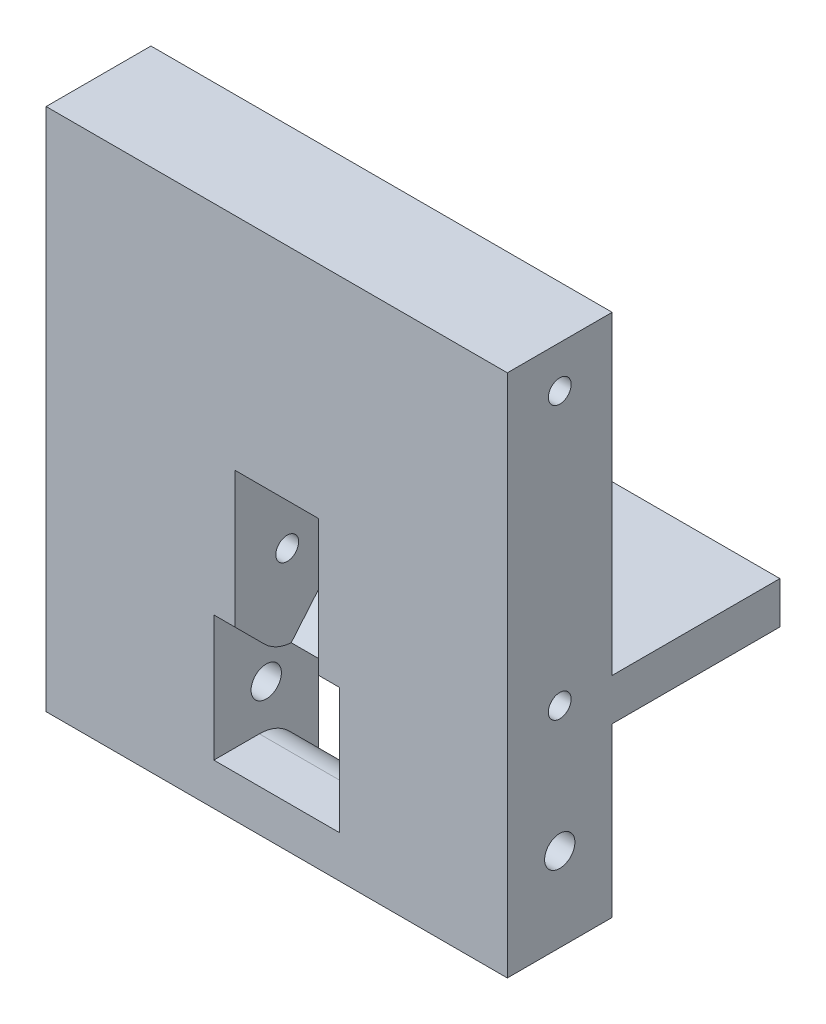
SolidWorks part; units mm, degrees
material "ABS"
ref_plane "Front Plane" through (0, 0, 0) normal (0, 0, 1) x (1, 0, 0)
ref_plane "Top Plane" through (0, 0, 0) normal (0, 1, 0) x (1, 0, 0)
ref_plane "Right Plane" through (0, 0, 0) normal (1, 0, 0) x (0, 0, -1)
sketch "Sketch2" plane through (-62.0532, 0, 0) normal (-1, 0, 0) x (0, 0, 1)
  line L1 (9.2122, 119.5977) -> (25.0872, 119.5977)
  line L2 (9.2122, 119.5977) -> (9.2122, 40.2227)
  line L3 (9.2122, 40.2227) -> (25.0872, 40.2227)
  line L4 (9.2122, 65.6227) -> (-92.3878, 65.6227)
  line L5 (-92.3878, 65.6227) -> (-92.3878, 59.2727)
  line L6 (-92.3878, 59.2727) -> (9.2122, 59.2727)
  line L7 (9.2122, 59.2727) -> (9.2122, 65.6227)
  line L8 (9.2122, 65.6227) -> (-92.3878, 65.6227)
  line L9 (-92.3878, 65.6227) -> (-92.3878, 59.2727)
  line L10 (-92.3878, 59.2727) -> (9.2122, 59.2727)
  line L11 (9.2122, 59.2727) -> (9.2122, 65.6227)
  line L12 (25.0872, 119.5977) -> (25.0872, 40.2227)
  line L13 (9.2122, 65.6227) -> (-16.1878, 65.6227)
  line L14 (9.2122, 65.6227) -> (9.2122, 71.9727)
  line L15 (9.2122, 71.9727) -> (-16.1878, 71.9727)
  line L16 (-16.1878, 65.6227) -> (-16.1878, 71.9727)
  line L17 (15.5622, 114.8352) -> (18.7372, 114.8352) construction
  line L18 (15.5622, 114.8352) -> (15.5622, 111.6602) construction
  line L19 (15.5622, 111.6602) -> (18.7372, 111.6602) construction
  line L20 (18.7372, 114.8352) -> (18.7372, 111.6602) construction
  line L21 (15.5622, 114.8352) -> (18.7372, 111.6602) construction
  line L22 (15.5622, 111.6602) -> (18.7372, 114.8352) construction
  line L23 (15.5622, 73.5602) -> (18.7372, 73.5602) construction
  line L24 (15.5622, 73.5602) -> (15.5622, 70.3852) construction
  line L25 (15.5622, 70.3852) -> (18.7372, 70.3852) construction
  line L26 (18.7372, 73.5602) -> (18.7372, 70.3852) construction
  line L27 (15.5622, 73.5602) -> (18.7372, 70.3852) construction
  line L28 (15.5622, 70.3852) -> (18.7372, 73.5602) construction
  circle A0 centre (17.1497, 71.9727) radius 2.3 construction
  circle A1 centre (17.1497, 113.2477) radius 1.7272
  circle A2 centre (17.1497, 71.9727) radius 1.7272
  line M10 (9.2122, 65.6227) -> (-92.3878, 65.6227)
  line M13 (9.2122, 59.2727) -> (9.2122, 65.6227)
  dimension "D5" = 4.6
  dimension "D8" = 3.4544
  dimension "D9" = 7.9375
  dimension "D10" = 3.175
  dimension "D7" = 6.35
  dimension "D15" = 3.4544
  dimension "D2" = 79.375
  dimension "D3" = 19.05
  dimension "D4" = 15.875
  dimension "D6" = 7.9375
  dimension "D11" = 25.4
  dimension "D12" = 6.35
  dimension "D13" = 3.175
  dimension "D14" = 41.275
  dimension "D1" = 0
extrude "Boss-Extrude1" add sketch "Sketch2" against normal blind 69.85 contours L16 L2 L15 M10 | L12 L1 L2 L3 A1 A0 M13 region at (-62.0532, 79.7185, 17.1497) region at (-62.0532, 68.7977, -3.4878)
sketch "Sketch3" plane through (0, 0, 9.2122) normal (0, 0, -1) x (-1, 0, 0)
  line L2 (17.6032, 46.5727) -> (36.6532, 46.5727)
  line L3 (17.6032, 46.5727) -> (17.6032, 59.2727)
  line L4 (62.0532, 40.2227) -> (62.0532, 65.6227)
  line L5 (62.0532, 65.6227) -> (-7.7968, 65.6227)
  line L6 (-7.7968, 65.6227) -> (-7.7968, 40.2227)
  line L7 (-7.7968, 40.2227) -> (62.0532, 40.2227)
  line L8 (62.0532, 40.2227) -> (62.0532, 65.6227)
  line L9 (62.0532, 65.6227) -> (-7.7968, 65.6227)
  line L10 (-7.7968, 65.6227) -> (-7.7968, 40.2227)
  line L11 (-7.7968, 40.2227) -> (62.0532, 40.2227)
  line L12 (17.6032, 59.2727) -> (36.6532, 59.2727)
  line L13 (36.6532, 46.5727) -> (36.6532, 59.2727)
  line L14 (17.6032, 46.5727) -> (36.6532, 59.2727) construction
  line L15 (17.6032, 59.2727) -> (36.6532, 46.5727) construction
  point P6 (27.1282, 40.2227)
  point P7 (27.1282, 52.9227)
  dimension "D2" = 19.05
  dimension "D3" = 12.7
  dimension "D4" = 12.7
  dimension "D1" = 0
extrude "Cut-Extrude1" cut sketch "Sketch3" against normal blind 127 contours L2 L13 L12 L3
sketch "Sketch4" plane through (7.7968, 0, 0) normal (1, 0, 0) x (0, 0, -1)
  line L0 (-9.2122, 40.2227) -> (-25.0872, 40.2227) construction
  line L1 (-25.0872, 52.9227) -> (-17.1497, 52.9227) construction
  line L2 (-25.0872, 52.9227) -> (-25.0872, 59.2727) construction
  line L3 (-25.0872, 59.2727) -> (-17.1497, 59.2727) construction
  line L4 (-17.1497, 52.9227) -> (-17.1497, 59.2727) construction
  line L5 (-25.0872, 46.5727) -> (-9.2122, 46.5727)
  line L7 (-9.2122, 46.5727) -> (-9.2122, 59.2727)
  line L8 (-9.2122, 59.2727) -> (-25.0872, 59.2727)
  line L9 (-25.0872, 59.2727) -> (-25.0872, 46.5727)
  line L10 (-25.0872, 46.5727) -> (-9.2122, 46.5727) construction
  line L12 (-9.2122, 46.5727) -> (-9.2122, 59.2727) construction
  line L13 (-9.2122, 59.2727) -> (-25.0872, 59.2727) construction
  line L14 (-25.0872, 59.2727) -> (-25.0872, 46.5727) construction
  circle A0 centre (-17.1497, 52.9227) radius 2.2951
  dimension "D2" = 4.5901
  dimension "D3" = 12.7
  dimension "D1" = 0
extrude "Cut-Extrude2" cut sketch "Sketch4" against normal blind 127 contours A0
chamfer "Chamfer1" distance 6.35 angle 45 2 edges at (-27.1282, 46.5727, 9.2122) (-27.1282, 59.2727, 25.0872)
fillet "Fillet2" radius 6.35 2 edges at (-27.1282, 46.5727, 15.5622) (-27.1282, 59.2727, 18.7372)
sketch "Sketch8" plane through (-27.1282, 59.2727, 33.483) normal (-1, 0, 0) x (0, 0, 1)
  line L0 (-24.2707, 12.7) -> (-49.6707, 12.7) construction
  line L1 (-24.2707, 12.7) -> (-49.6707, 12.7)
  line L2 (-2.8258, 22.4609) -> (-2.8258, 22.4965)
  line L3 (-15.9276, 35.8951) -> (9.2394, 5.9023)
  line L4 (9.2394, 5.9023) -> (-7.0779, -7.7896)
  line L5 (-7.0779, -7.7896) -> (-20.0855, 7.7123)
  line L6 (-20.0855, 7.7123) -> (-24.2707, 12.7)
  line L7 (-7.0779, -7.7896) -> (-24.2707, 12.7)
  line L8 (-7.0779, -7.7896) -> (-9.0237, -9.4222)
  line L9 (-24.2707, 12.7) -> (-26.2165, 11.0673)
  line L10 (-9.0237, -9.4222) -> (-26.2165, 11.0673)
  line L11 (-26.2165, 11.0673) -> (-27.5864, 12.7)
  circle A0 centre (-30.5207, 23.65) radius 2.4 construction
  circle A1 centre (-30.5207, 23.65) radius 2.4
  circle A2 centre (-30.5207, 23.65) radius 19.05
  dimension "D1" = 38.1
  dimension "D2" = 130
  dimension "D3" = 2.54
extrude "Cut-Extrude3" cut sketch "Sketch8" against normal blind 6.35 and the other way blind 6.35 contours A2 L10 L8 L5 | L10 A2 L6 L9 | L11 L9 L1 | A2 L5 L4 L3 | L6 A2 L1 A1 region at (-27.1282, 71.4285, 7.4584) region at (-27.1282, 72.49, 7.5544) region at (-27.1282, 68.752, 10.2779) region at (-27.1282, 68.3478, 27.4388) region at (-27.1282, 58.4952, 18.8569)
sketch "Sketch10" plane through (0, 0, 9.2122) normal (0, 0, -1) x (-1, 0, 0)
  line L0 (33.4782, 71.9727) -> (62.0532, 71.9727) construction
  line L1 (41.4998, 71.9727) -> (51.0248, 71.9727)
  line L2 (41.4998, 71.9727) -> (41.4998, 76.6717)
  line L3 (41.4998, 76.6717) -> (51.0248, 76.6717)
  line L4 (51.0248, 71.9727) -> (51.0248, 76.6717)
  line L5 (41.4998, 104.6609) -> (51.0248, 104.6609)
  line L6 (41.4998, 104.6609) -> (41.4998, 99.9619)
  line L7 (41.4998, 99.9619) -> (51.0248, 99.9619)
  line L8 (51.0248, 104.6609) -> (51.0248, 99.9619)
  line L9 (62.0532, 119.5977) -> (62.0532, 71.9727) construction
  dimension "D1" = 20.5534
  dimension "D2" = 23.2902
  dimension "D3" = 4.699
  dimension "D4" = 9.525
extrude "Boss-Extrude2" add sketch "Sketch10" along normal blind 12.7
sketch "Sketch12" plane through (-41.4998, 0, 0) normal (1, 0, 0) x (0, 0, -1)
  line L0 (-2.8622, 74.8168) -> (-2.8622, 101.8168) construction
  line L1 (3.4878, 76.6717) -> (3.4878, 99.9619) construction
  line L2 (3.4878, 104.6609) -> (3.4878, 99.9619) construction
  line L3 (3.4878, 99.9619) -> (-9.2122, 99.9619) construction
  circle A0 centre (-2.8622, 101.8168) radius 0.8763
  circle A1 centre (-2.8622, 74.8168) radius 0.8763
  point P11 (3.4878, 88.3168)
  point P12 (-2.8622, 88.3168)
  dimension "D1" = 1.7526
  dimension "D2" = 27
extrude "Cut-Extrude4" cut sketch "Sketch12" against normal through all
